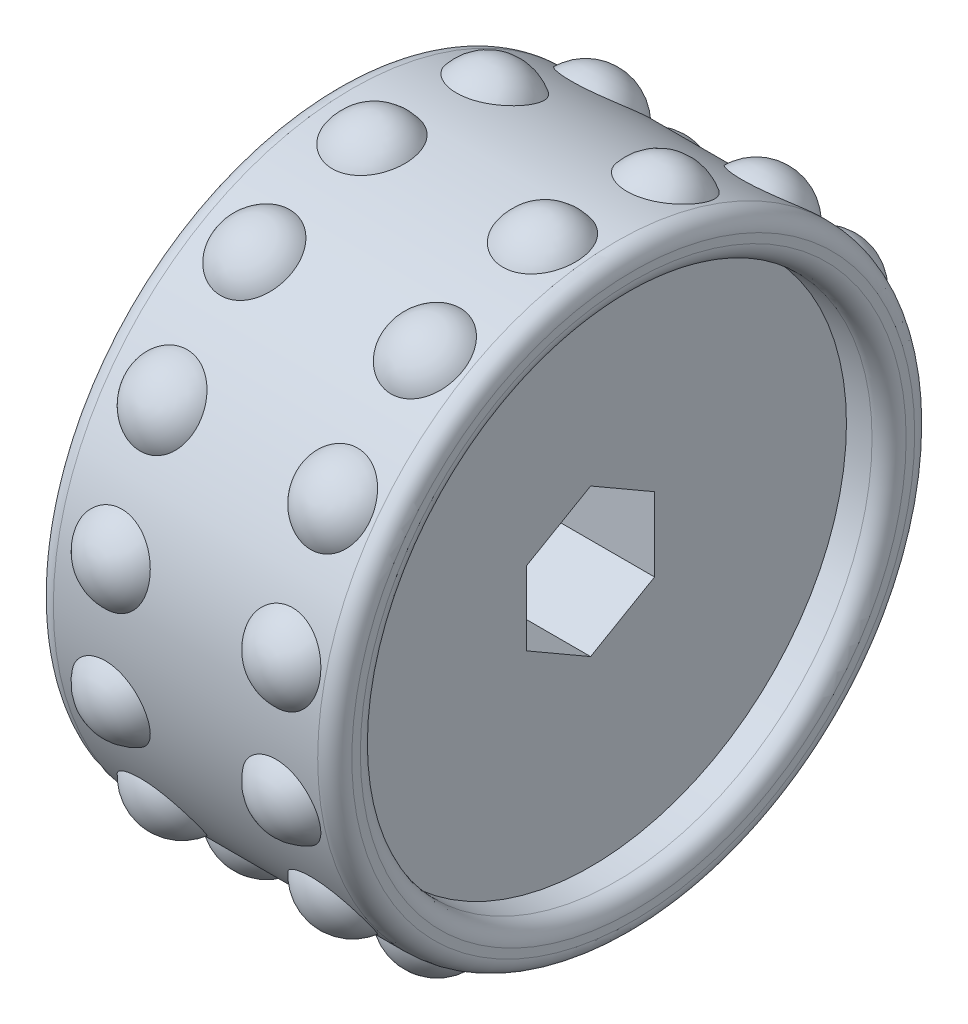
SolidWorks part; units mm, degrees
note: The reader was unsure of these and kept them because the rebuilt part matched: shared geometry of "Sketch1<4>", "Sketch1<6>".
material "Chrome Stainless Steel"
ref_plane "Front Plane" through (0, 0, 0) normal (0, 0, 1) x (1, 0, 0)
ref_plane "Top Plane" through (0, 0, 0) normal (0, 1, 0) x (1, 0, 0)
ref_plane "Right Plane" through (0, 0, 0) normal (1, 0, 0) x (0, 0, -1)
sketch "Sketch1" plane through (0, 0, 0) normal (1, 0, 0) x (0, 0, -1)
  line L1 (1.5, -0.866) -> (1.5, 0.866)
  line L2 (1.5, 0.866) -> (0, 1.7321)
  line L3 (0, 1.7321) -> (-1.5, 0.866)
  line L4 (-1.5, 0.866) -> (-1.5, -0.866)
  line L5 (-1.5, -0.866) -> (0, -1.7321)
  line L6 (0, -1.7321) -> (1.5, -0.866)
  circle A0 centre (0, 0) radius 7
  circle A1 centre (0, 0) radius 6
  circle A2 centre (0, 0) radius 1.5 construction
  dimension "D1" = 14
  dimension "D2" = 12
  dimension "D3" = 3
extrude "Boss-Extrude1" add sketch "Sketch1" along normal blind 7 contours A0
extrude "Cut-Extrude2" cut sketch "Sketch1<4>" against normal blind 1 from surface at 7 contours A1 starting at face at (7, 0, -7)
sketch "Sketch1<4>" plane through (0, 0, 0) normal (1, 0, 0) x (0, 0, -1) same geometry as "Sketch1"
extrude "Cut-Extrude3" cut sketch "Sketch1<6>" against normal through all from surface at 6 contours L4 L5 L6 L1 L2 L3 starting at face at (6, 0, -6)
sketch "Sketch1<6>" plane through (0, 0, 0) normal (1, 0, 0) x (0, 0, -1) same geometry as "Sketch1"
ref_plane "Plane1" through (1.6, 0, 0) normal (-1, 0, 0) x (0, 0, 1)
sketch "Sketch2" plane through (1.6, 0, 0) normal (1, 0, 0) x (0, 0, -1)
  line L0 (7, 0) -> (7.4788, 0)
  arc A0 (6.9372, 0.9355) -> (7.4788, 0) centre (6.4, 0) cw
  circle A1 centre (0, 0) radius 7 construction
  arc A2 (7, 0) -> (6.9372, 0.9355) centre (0, 0) ccw
  point P7 (7, 0)
  dimension "D1" = 1.0788
  dimension "D2" = 0.6
revolve "Revolve1" add sketch "Sketch2" angle 360 about L0
ref_plane "Plane2" through (5.6, 0, 0) normal (1, 0, 0) x (0, 0, -1)
sketch "Sketch3" plane through (5.6, 0, 0) normal (1, 0, 0) x (0, 0, -1)
  line L1 (7, 0) -> (7.4788, 0)
  line L2 (7, 0) -> (7.4788, 0)
  arc A2 (7.4788, 0) -> (6.9372, 0.9355) centre (6.4, 0) ccw
  arc A3 (7, 0) -> (6.9372, 0.9355) centre (0, 0) ccw
  arc A4 (7.4788, 0) -> (6.9372, 0.9355) centre (6.4, 0) ccw
  arc A5 (7, 0) -> (6.9372, 0.9355) centre (0, 0) ccw
  dimension "D1" = 0
revolve "Revolve2" add sketch "Sketch3" angle 360 about L2
pattern_circular "CirPattern1" count 15 every 24 about axis through (0, 0, 0) along (1, 0, 0) of "Revolve1", "Revolve2"
fillet "Fillet1" radius 0.4 3 edges at (0, 0, -7) (7, 0, -7) (7, 0, -6)
